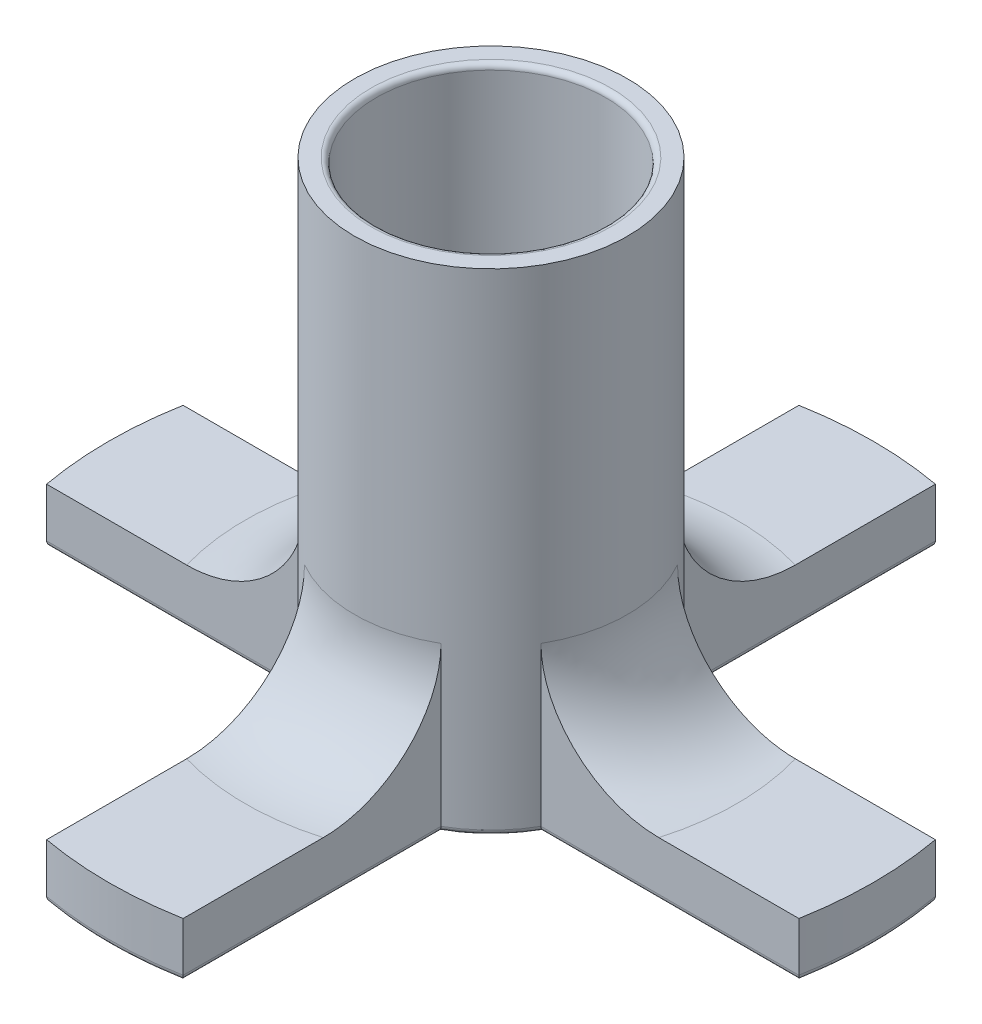
SolidWorks part; units mm, degrees
ref_plane "Front" through (0, 0, 0) normal (0, 0, 1) x (1, 0, 0)
ref_plane "Top" through (0, 0, 0) normal (0, 1, 0) x (1, 0, 0)
ref_plane "Right" through (0, 0, 0) normal (1, 0, 0) x (0, 0, -1)
sketch "Sketch1" plane through (0, 0, 0) normal (0, 1, 0) x (1, 0, 0)
  line L0 (-70, 0) -> (70, 0) construction
  line L1 (0, 70) -> (0, -70) construction
  line L2 (-68.8749, 12.5) -> (-21.6506, 12.5)
  line L3 (-68.8749, -12.5) -> (-21.6506, -12.5)
  line L4 (12.5, 68.8749) -> (12.5, 21.6506)
  line L5 (-12.5, 68.8749) -> (-12.5, 21.6506)
  line L6 (68.8749, -12.5) -> (21.6506, -12.5)
  line L7 (68.8749, 12.5) -> (21.6506, 12.5)
  line L8 (-12.5, -68.8749) -> (-12.5, -21.6506)
  line L9 (12.5, -68.8749) -> (12.5, -21.6506)
  arc A0 (-68.8749, 12.5) -> (-68.8749, -12.5) centre (0, 0) ccw
  arc A1 (-21.6506, -12.5) -> (-12.5, -21.6506) centre (0, 0) ccw
  arc A2 (-12.5, 21.6506) -> (-21.6506, 12.5) centre (0, 0) ccw
  arc A3 (21.6506, 12.5) -> (12.5, 21.6506) centre (0, 0) ccw
  arc A4 (12.5, -21.6506) -> (21.6506, -12.5) centre (0, 0) ccw
  arc A5 (12.5, 68.8749) -> (-12.5, 68.8749) centre (0, 0) ccw
  arc A6 (68.8749, -12.5) -> (68.8749, 12.5) centre (0, 0) ccw
  arc A7 (-12.5, -68.8749) -> (12.5, -68.8749) centre (0, 0) ccw
  point P27 (0, 0)
  dimension "D1" = 140
  dimension "D2" = 50
  dimension "D3" = 25
  dimension "D4" = 4
extrude "Boss-Extrude1" add sketch "Sketch1" along normal blind 10
sketch "Sketch2" plane through (0, 10, 0) normal (0, 1, 0) x (1, 0, 0)
  circle A0 centre (0, 0) radius 25
  circle A1 centre (0, 0) radius 21
  dimension "D1" = 42
extrude "Boss-Extrude2" add sketch "Sketch2" along normal blind 80
fillet "Fillet1" radius 1 17 edges at (-45.2628, 0, 12.5) (-17.6777, 0, 17.6777) (-12.5, 0, 45.2628) (0, 0, 70) (12.5, 0, 45.2628) (17.6777, 0, 17.6777) (45.2628, 0, 12.5) (70, 0, 0) (45.2628, 0, -12.5) (17.6777, 0, -17.6777) (12.5, 0, -45.2628) (0, 0, -70) (-12.5, 0, -45.2628) (-17.6777, 0, -17.6777) (-45.2628, 0, -12.5) (-70, 0, 0) (0, 90, 21)
fillet "Fillet2" radius 20 4 edges at (-25, 10, 0) (0, 10, -25) (25, 10, 0) (0, 10, 25)
